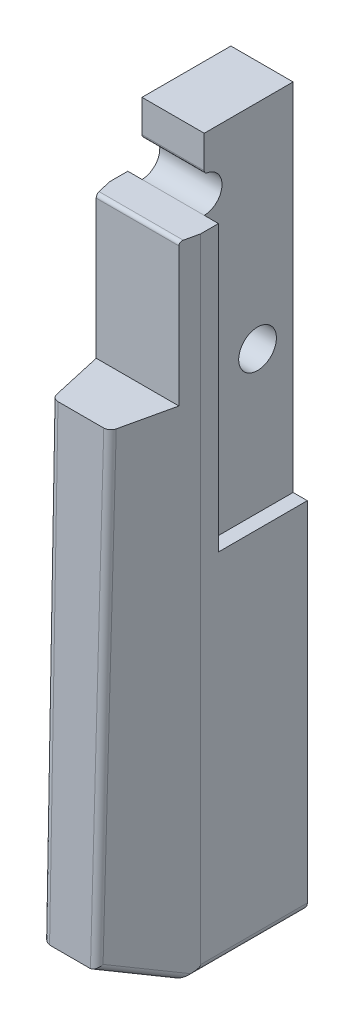
SolidWorks part; units mm, degrees
ref_plane "Front Plane" through (0, 0, 0) normal (1, 0, 0) x (0, 1, 0)
ref_plane "Top Plane" through (0, 0, 0) normal (0, 0, 1) x (0, 1, 0)
ref_plane "Right Plane" through (0, 0, 0) normal (0, 1, 0) x (-1, 0, 0)
sketch "Sketch1" plane through (0, 0, 0) normal (0, 0, 1) x (0, 1, 0)
  line L1 (0, 0) -> (100, 0)
  line L2 (0, 0) -> (0, 11.75)
  line L3 (0, 11.75) -> (100, 11.75)
  line L4 (100, 0) -> (100, 11.75)
  dimension "D1" = 100
  dimension "D2" = 11.75
extrude "Boss-Extrude1" add sketch "Sketch1" along normal blind 17.5
sketch "Sketch5" plane through (0, 0, 0) normal (1, 0, 0) x (0, 1, 0)
  line L1 (100, 17.5) -> (70, 17.5)
  line L2 (100, 17.5) -> (100, 5)
  line L3 (100, 5) -> (70, 5)
  line L4 (70, 17.5) -> (70, 5)
  circle A0 centre (70, 5) radius 2.65
  dimension "D1" = 30
extrude "Cut-Extrude2" cut sketch "Sketch5" against normal through all contours A0
sketch "Sketch4" plane through (0, 0, 0) normal (1, 0, 0) x (0, 1, 0)
  line L0 (100, 17.5) -> (100, 12.5)
  line L1 (100, 17.5) -> (100, 0) construction
  line L3 (100, 12.5) -> (50, 12.5)
  line L4 (100, 12.5) -> (100, 0)
  line L5 (100, 0) -> (50, 0)
  line L6 (50, 12.5) -> (50, 0)
  line M6 (0, 0) -> (100, 0)
  line M7 (100, 0) -> (100, 17.5)
  circle M10 centre (70, 5) radius 2.65
  dimension "D1" = 50
  dimension "D2" = 12.5
extrude "Cut-Extrude3" cut sketch "Sketch4" against normal blind 1.5 contours L3 L6 M6 M7 M10 region at (0, 75.183, 6.2957)
ref_plane "Plane1" through (-5.875, 0, 0) normal (1, 0, 0) x (0, 0, -1)
mirror "Mirror1" about plane through (-5.875, 0, 0) normal (1, 0, 0) of "Cut-Extrude3"
sketch "Sketch9" plane through (0, 0, 0) normal (1, 0, 0) x (0, 1, 0)
  line L1 (0, 17.5) -> (50, 17.5)
  line L2 (0, 17.5) -> (0, 0)
  line L3 (0, 0) -> (50, 0)
  line L4 (50, 12.5) -> (50, 0)
  line L5 (50, 17.5) -> (100, 17.5)
  line L7 (50, 12.5) -> (100, 12.5)
  line L8 (100, 17.5) -> (100, 12.5)
extrude "Boss-Extrude3" add sketch "Sketch9" along normal blind 0.5
mirror "Mirror4" about plane through (-5.875, 0, 0) normal (1, 0, 0) of "Boss-Extrude3"
sketch "Sketch6" plane through (0.5, 0, 0) normal (1, 0, 0) x (0, 1, 0)
  line L0 (0, 17.5) -> (4.75, 27)
  line L1 (4.75, 27) -> (90, 25)
  line L2 (90, 25) -> (100, 17.5)
  line L4 (70, 5) -> (70, 12.5) construction
  line L5 (70, 12.5) -> (70, 25.4692)
  line L6 (0, 17.5) -> (0, 0)
  line L7 (0, 0) -> (50, 0)
  line L8 (50, 0) -> (50, 12.5)
  line L9 (50, 12.5) -> (100, 12.5)
  line L12 (100, 12.5) -> (100, 17.5)
extrude "Boss-Extrude2" add sketch "Sketch6" against normal blind 12.75 contours L5 L1 L0 region at (0.5, 31.0716, 14.0937)
sketch "Sketch7" plane through (0, 100, 0) normal (0, 1, 0) x (-1, 0, 0)
  line L0 (-0.5, 15) -> (12.25, 15) construction
  line L1 (1.5, 0) -> (10.25, 0) construction
  line L2 (1.5, 0) -> (1.5, 17.5) construction
  line L3 (1.5, 17.5) -> (10.25, 17.5) construction
  line L4 (10.25, 0) -> (10.25, 17.5) construction
  line L7 (-0.5, 15) -> (2.202, 27)
  line L8 (12.25, 27) -> (-0.5, 27) construction
  line L9 (12.25, 12.5) -> (12.25, 17.5) construction
  line L10 (-0.5, 12.5) -> (-0.5, 17.5) construction
  line L11 (-0.5, 17.5) -> (-0.5, 15) construction
  line L12 (12.25, 17.5) -> (12.25, 15) construction
extrude "Cut-Extrude4" cut sketch "Sketch7" against normal through all and the other way through all
mirror "Mirror3" about plane through (-5.875, 0, 0) normal (1, 0, 0) of "Cut-Extrude4"
fillet "Fillet4" radius 1 5 edges at (-10.6175, 2.375, 22.25) (-5.875, 0, 17.5) (-1.1325, 2.375, 22.25) (-2.0297, 37.375, 26.2346) (-9.7203, 37.375, 26.2346)
fillet "Fillet3" radius 1 2 edges at (-12.25, 0, 7.5) (0.5, 0, 7.5)
sketch "Sketch11" plane through (0.5, 95.8808, 19.3496) normal (1, 0, 0) x (0, 0, 1)
  line L0 (-6.8496, 45.8808) -> (-6.8496, -4.1192) construction
  line L5 (-1.8496, -4.1192) -> (-6.8496, -4.1192)
  line L8 (-1.8496, -4.1192) -> (-1.8496, 3.3808)
  line L9 (-1.8496, 3.3808) -> (-6.8496, 3.3808)
  line L10 (-6.8496, -4.1192) -> (-6.8496, 3.3808)
  line L11 (-1.8496, 3.3808) -> (-6.8496, 3.3808) construction
  line L12 (-1.8496, 0.8808) -> (-6.8496, 0.8808)
  line L13 (-1.8496, 5.8808) -> (-6.8496, 5.8808)
  arc A4 (-1.8496, 0.8808) -> (-1.8496, 5.8808) centre (-1.8496, 3.3808) ccw
  arc A5 (-6.8496, 5.8808) -> (-6.8496, 0.8808) centre (-6.8496, 3.3808) ccw
  point P7 (-4.3496, 3.3808)
extrude "Cut-Extrude5" cut sketch "Sketch11" against normal up to next contours A4 L13 A5 L12
sketch "Sketch12" plane through (0, 0, 0) normal (0, 0, -1) x (1, 0, 0)
  line L0 (-11.25, 0) -> (-0.5, 0) construction
  line L1 (0.5, 0) -> (-5.875, 0)
  line L2 (0.5, 0) -> (0.5, -13.5)
  line L3 (0.5, -13.5) -> (-5.875, -13.5)
  line L4 (-5.875, 0) -> (-5.875, -13.5)
  circle A0 centre (-5.875, -13.5) radius 3
  dimension "D4" = 6
  dimension "D1" = 13.5
  dimension "D2" = 6.375
extrude "Cut-Extrude6" cut sketch "Sketch12" against normal blind 5 contours A0
sketch "Sketch13" plane through (0.5, 0, 0) normal (1, 0, 0) x (0, 1, 0)
  line L1 (100, 12.5) -> (95, 12.5)
  line L2 (100, 12.5) -> (100, 17.5)
  line L3 (100, 17.5) -> (95, 17.5)
  line L4 (95, 12.5) -> (95, 17.5)
extrude "Cut-Extrude7" cut sketch "Sketch13" against normal up to next
fillet "Fillet5" radius 0.5 2 edges at (-5.875, 90, 17.5) (-5.875, 95, 12.5)
equation "\"whitekey_cutout_length\"= 101.5"
equation "\"mount_recess_length\"=50"
equation "\"mount_recess_height\"=12.5"
equation "\"mount_recess_depth\"=1.5"
equation "\"D1@Sketch4\"=\"mount_recess_length\""
equation "\"D2@Sketch4\"=\"mount_recess_height\""
equation "\"D1@Cut-Extrude3\"=\"mount_recess_depth\""
equation "\"D1@Sketch5\"=\"mount_recess_length\"-20"
equation "\"D1@Sketch1\"=\"whitekey_cutout_length\"-1.5"
